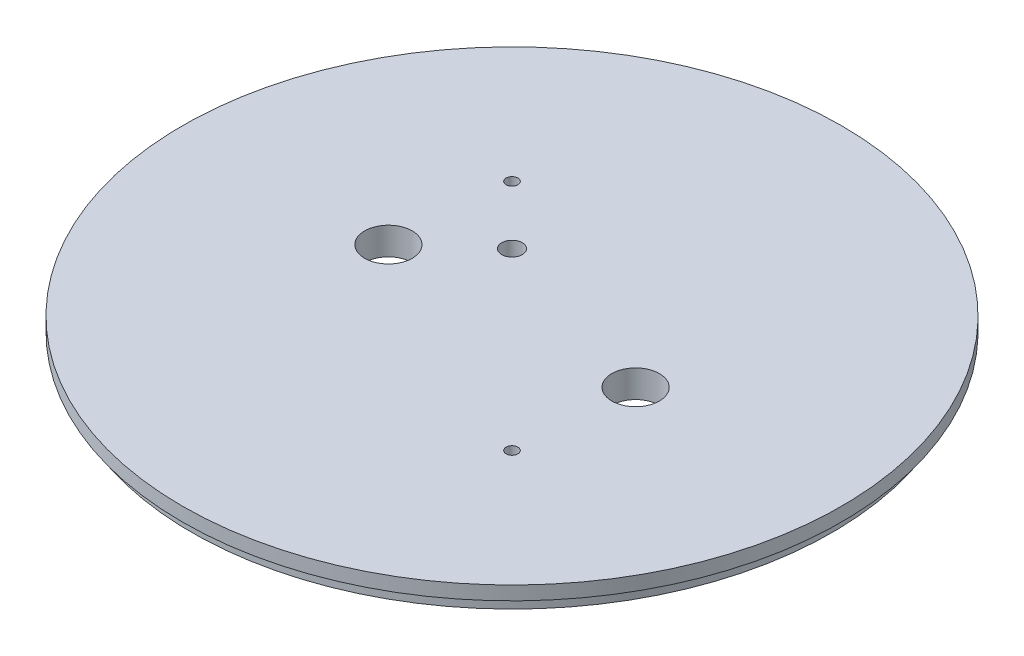
SolidWorks part; units mm, degrees
material "6061-T6 (SS)"
ref_plane "Front Plane" through (0, 0, 0) normal (0, 0, 1) x (1, 0, 0)
ref_plane "Top Plane" through (0, 0, 0) normal (0, 1, 0) x (1, 0, 0)
ref_plane "Right Plane" through (0, 0, 0) normal (1, 0, 0) x (0, 0, -1)
sketch "Sketch1" plane through (0, 0, 0) normal (0, 1, 0) x (1, 0, 0)
  line L0 (0, -76.2) -> (0, 76.2) construction
  line L1 (-76.2, 0) -> (76.2, 0) construction
  line L2 (-26.9408, 26.9408) -> (0, 0) construction
  line L3 (0, 56.7387) -> (0, 29.6936) construction
  line L4 (3.6407, 56.7387) -> (3.6407, 29.6936) construction
  line L5 (-3.6407, 56.7387) -> (-3.6407, 29.6936) construction
  line L6 (0, -56.7387) -> (0, -29.6936) construction
  line L7 (3.6407, -56.7387) -> (3.6407, -29.6936) construction
  line L8 (-3.6407, -56.7387) -> (-3.6407, -29.6936) construction
  line L9 (-53.8815, -53.8815) -> (54.3236, 54.3236) construction
  circle A0 centre (0, 0) radius 76.2
  circle A1 centre (0, 0) radius 3.175 construction
  circle A2 centre (28.575, 0) radius 5.5
  circle A3 centre (-28.575, 0) radius 5.5
  circle A4 centre (-26.9408, 26.9408) radius 1.3589
  arc A6 (3.6407, 56.7387) -> (-3.6407, 56.7387) centre (0, 56.7387) ccw construction
  arc A7 (-3.6407, 29.6936) -> (3.6407, 29.6936) centre (0, 29.6936) ccw construction
  arc A8 (3.6407, -56.7387) -> (-3.6407, -56.7387) centre (0, -56.7387) cw construction
  arc A9 (-3.6407, -29.6936) -> (3.6407, -29.6936) centre (0, -29.6936) cw construction
  circle A10 centre (26.9408, -26.9408) radius 1.3589
  circle A11 centre (-13.4704, 13.4704) radius 2.3813
  point P16 (0, 43.2162)
  point P19 (0, 0)
  point P26 (0, -43.2162)
  dimension "D1" = 152.4
  dimension "D2" = 6.35
  dimension "D3" = 11
  dimension "D5" = 2.7178
  dimension "D8" = 4.7625
  dimension "D6" = 38.1
  dimension "D7" = 45
  dimension "D4" = 45
  dimension "D9" = 28.575
extrude "Boss-Extrude1" add sketch "Sketch1" along normal blind 6.35
sketch "Sketch2" plane through (0, 0, 0) normal (0, -1, 0) x (1, 0, 0)
  circle A0 centre (0, 0) radius 76.2
  circle A1 centre (0, 0) radius 74.041
  dimension "D1" = 152.4
  dimension "D2" = 148.082
extrude "Cut-Extrude1" cut sketch "Sketch2" against normal blind 3.175
sketch "Sketch3" plane through (0, 6.35, 0) normal (0, 1, 0) x (1, 0, 0)
  line L0 (0, 76.2) -> (0, -76.2) construction
  line L1 (-76.2, 0) -> (76.2, 0) construction
  line L2 (0, 34.798) -> (0, 13.97) construction
  line L3 (3.2385, 34.798) -> (3.2385, 13.97)
  line L4 (-3.2385, 34.798) -> (-3.2385, 13.97)
  line L5 (0, -34.798) -> (0, -13.97) construction
  line L6 (3.2385, -34.798) -> (3.2385, -13.97)
  line L7 (-3.2385, -34.798) -> (-3.2385, -13.97)
  circle A0 centre (0, 0) radius 76.2 construction
  arc A1 (3.2385, 34.798) -> (-3.2385, 34.798) centre (0, 34.798) ccw
  arc A2 (-3.2385, 13.97) -> (3.2385, 13.97) centre (0, 13.97) ccw
  arc A3 (3.2385, -34.798) -> (-3.2385, -34.798) centre (0, -34.798) cw
  arc A4 (-3.2385, -13.97) -> (3.2385, -13.97) centre (0, -13.97) cw
  point P7 (0, 13.97)
  point P8 (0, 34.798)
  point P12 (0, 24.384)
  point P20 (0, -24.384)
  point P25 (0, -34.798)
  point P26 (0, -13.97)
  dimension "D1" = 13.97
  dimension "D2" = 20.828
  dimension "D3" = 6.477
extrude "Cut-Extrude2" cut sketch "Sketch3" against normal blind 3.556 from offset 5.969 offset against normal yes
equation "\"leadDist\"=1.5"
equation "\"Lead_Screw_Dist\"= 2.25in"
equation "\"D9@Sketch1\"=\"Lead_Screw_Dist\"/2"
equation "\"Lead_Screw_Diam\"= 11mm"
equation "\"D3@Sketch1\"=\"Lead_Screw_Diam\""
